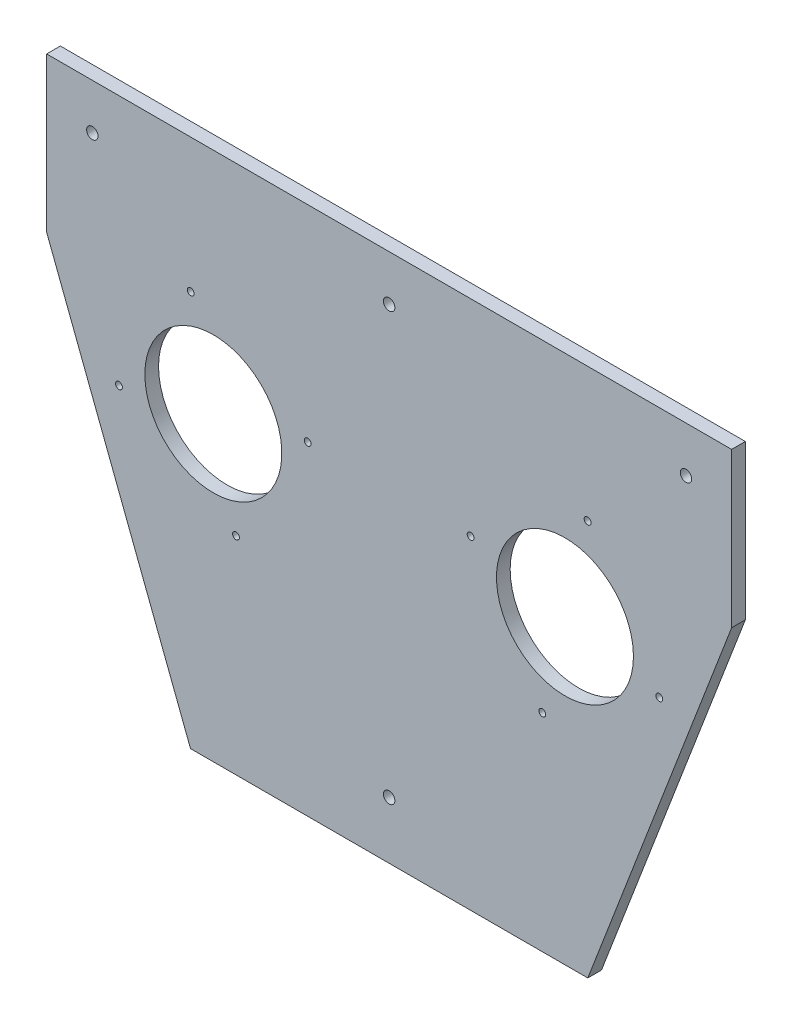
SolidWorks part; units mm, degrees
ref_plane "Front Plane" through (0, 0, 0) normal (0, 0, 1) x (1, 0, 0)
ref_plane "Top Plane" through (0, 0, 0) normal (0, 1, 0) x (1, 0, 0)
ref_plane "Right Plane" through (0, 0, 0) normal (1, 0, 0) x (0, 0, -1)
sketch "Sketch1" plane through (0, 0, 0) normal (0, 0, 1) x (1, 0, 0)
  line L0 (-130, 93.5) -> (130, 93.5) construction
  line L1 (-150, 45.8381) -> (-87, -118.5)
  line L2 (-87, -118.5) -> (87, -118.5)
  line L3 (87, -118.5) -> (150, 45.8381)
  line L4 (0, -93.5) -> (0, -118.5) construction
  line L6 (0, -93.5) -> (0, 93.5) construction
  line L7 (-150, 113.5) -> (150, 113.5)
  line L8 (150, 113.5) -> (150, 45.8381)
  line L11 (-150, 45.8381) -> (-150, 113.5)
  circle A4 centre (0, -93.5) radius 2.5
  circle A20 centre (0, 93.5) radius 2.5
  circle A21 centre (-130, 93.5) radius 2.5
  circle A22 centre (130, 93.5) radius 2.5
  point P12 (0, 93.5)
  point P45 (0, 113.5)
  dimension "D2" = 5
  dimension "D9" = 260
  dimension "D3" = 20
  dimension "D6" = 20
  dimension "D1" = 25
  dimension "D4" = 174
  dimension "D5" = 176
  dimension "D7" = 187
extrude "Boss-Extrude1" add sketch "Sketch1" along normal blind 6
sketch "Sketch2" plane through (0, 0, 6) normal (0, 0, 1) x (1, 0, 0)
  line L0 (118.326, 3.5796) -> (35.674, 23.4204) construction
  line L1 (67.0796, -27.826) -> (86.9204, 54.826) construction
  line L2 (0, 0) -> (0, 93.5) construction
  line L3 (150, 113.5) -> (-150, 113.5) construction
  circle A0 centre (77, 13.5) radius 42.5 construction
  circle A1 centre (35.674, 23.4204) radius 1.5
  circle A2 centre (86.9204, 54.826) radius 1.5
  circle A3 centre (118.326, 3.5796) radius 1.5
  circle A4 centre (67.0796, -27.826) radius 1.5
  circle A5 centre (77, 13.5) radius 30
  circle A6 centre (-35.674, 23.4204) radius 1.5
  circle A7 centre (-86.9204, 54.826) radius 1.5
  circle A8 centre (-67.0796, -27.826) radius 1.5
  circle A9 centre (-118.326, 3.5796) radius 1.5
  circle A10 centre (-77, 13.5) radius 42.5 construction
  circle A11 centre (-77, 13.5) radius 30
  point P6 (77, 13.5)
  point P27 (-77, 13.5)
  dimension "D1" = 85
  dimension "D2" = 3
  dimension "D3" = 60
  dimension "D4" = 100
  dimension "D5" = 77
extrude "Cut-Extrude1" cut sketch "Sketch2" against normal blind 10
equation "\"carbon_fiber_tube_diam\"= 1in, 25.4mm"
equation "\"clip_tube_diam\"= 6mm"
equation "\"middle_tube_len\"= 500mm"
equation "\"horizontal_pipe_spacing\"= 260mm"
equation "\"D9@Sketch1\"=\"horizontal_pipe_spacing\""
equation "\"belly_plate_width\" = 176mm"
equation "\"belly_bottom_width\" = 170.267mm"
equation "\"belly_length\"  = 500mm"
